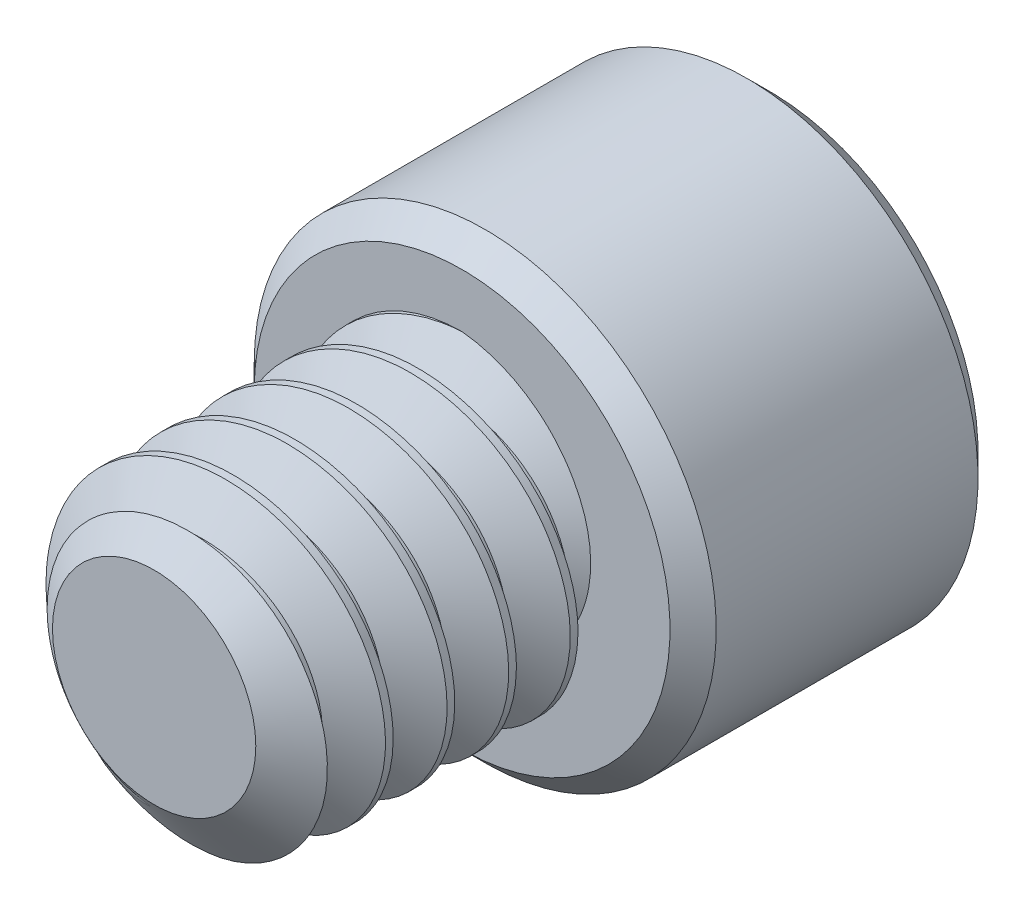
SolidWorks part; units mm, degrees
ref_plane "Front Plane" through (0, 0, 0) normal (0, 0, 1) x (1, 0, 0)
ref_plane "Top Plane" through (0, 0, 0) normal (0, 1, 0) x (1, 0, 0)
ref_plane "Right Plane" through (0, 0, 0) normal (1, 0, 0) x (0, 0, -1)
sketch "Sketch1" plane through (0, 0, 0) normal (0, 0, 1) x (1, 0, 0)
  circle A0 centre (0, 0) radius 3.175
  dimension "OD" = 6.35
extrude "Extrude1" add sketch "Sketch1" against normal blind 6.35
sketch "Sketch2" plane through (0, 0, 0) normal (0, 0, 1) x (1, 0, 0)
  circle A0 centre (0, 0) radius 3.175 construction
  circle A1 centre (0, 0) radius 3.175
curve "Helix/Spiral1" pitch 1.27 height 7.62 turns 6 parameters "pitch"=1.27
sketch "Sketch3" plane through (0, 0, 0) normal (1, 0, 0) x (0, 0, -1)
  line L0 (-1.1113, 3.175) -> (-0.635, 2.3501)
  line L1 (-0.635, 2.3501) -> (-0.4763, 2.3501)
  line L2 (-0.4763, 2.3501) -> (0, 3.175)
  line L3 (-1.1113, 3.175) -> (0, 3.175)
  line L4 (-0.5556, 3.175) -> (-0.5556, 2.3501) construction
  line L5 (-0.8731, 2.7626) -> (-0.2381, 2.7626) construction
  line L6 (0, 3.175) -> (0, -3.175) construction
  dimension "D1" = 0.1588
  dimension "D2" = 0.635
  dimension "D3" = 60
sweep "Cut-Sweep1" cut profiles "Sketch3" path "Helix/Spiral1"
sketch "Sketch4" plane through (0, 0, 0) normal (1, 0, 0) x (0, 0, -1)
  line L0 (0.7554, 3.175) -> (0, 2.0961)
  line L1 (0, 2.0961) -> (0, 3.175)
  line L2 (0.7554, 3.175) -> (0, 3.175)
  line L3 (-1.1113, 3.175) -> (0, 3.175) construction
  line L4 (0, 0) -> (7.0209, 0) construction
  dimension "D1" = 55
  dimension "D2" = 0.254
revolve "Cut-Revolve1" cut sketch "Sketch4" angle 360 about L4
sketch "Sketch5" plane through (0, 0, 0) normal (1, 0, 0) x (0, 0, -1)
  line L0 (6.35, -2.3728) -> (6.35, 2.2654) construction
  line L1 (6.35, 3.302) -> (87.4327, 3.302)
  line L2 (6.35, 3.302) -> (6.35, 0)
  line L3 (6.35, 0) -> (87.3125, 0)
  line L4 (87.3125, 2.9718) -> (87.3125, 0)
  line L5 (87.4327, 3.302) -> (87.3125, 2.9718)
  line L6 (0, 0) -> (9.9695, 0) construction
  point P3 (87.3125, 3.302)
  point P10 (87.3125, 3.302)
  dimension "D1" = 0.3302
  dimension "Thread min" = 87.3125
  dimension "D2" = 0.127
  dimension "D3" = 20
revolve "partially thread" [suppressed] add sketch "Sketch5" angle 360 about L6
sketch "Sketch6" plane through (0, 0, -6.35) normal (0, 0, -1) x (-1, 0, 0)
  circle A0 centre (0, 0) radius 4.7625
  dimension "head dia" = 9.525
extrude "Extrude2" add sketch "Sketch6" along normal blind 6.35
sketch "Sketch7" plane through (0, 0, -12.7) normal (0, 0, -1) x (-1, 0, 0)
  line L1 (0, 2.7496) -> (-2.3812, 1.3748)
  line L2 (-2.3812, 1.3748) -> (-2.3812, -1.3748)
  line L3 (-2.3812, -1.3748) -> (0, -2.7496)
  line L4 (0, -2.7496) -> (2.3813, -1.3748)
  line L5 (2.3813, -1.3748) -> (2.3813, 1.3748)
  line L6 (2.3813, 1.3748) -> (0, 2.7496)
  circle A0 centre (0, 0) radius 2.3813 construction
  dimension "hex dia" = 4.7625
extrude "Cut-Extrude1" cut sketch "Sketch7" against normal blind 3.5719
sketch "Sketch8" plane through (0, 0, -12.7) normal (0, 0, -1) x (-1, 0, 0)
  circle A0 centre (0, 0) radius 2.7496
extrude "Cut-Extrude2" cut sketch "Sketch8" against normal through all draft 45
chamfer "Chamfer1" distance 0.4763 angle 45 2 edges at (-4.7625, 0, -12.7) (-4.7625, 0, -6.35)
sketch "Sketch9" plane through (0, 0, 0) normal (1, 0, 0) x (0, 0, -1)
  line L0 (0, 3.175) -> (0, -3.175) construction
  line L1 (6.985, 3.175) -> (6.985, -3.175) construction
  dimension "D1" = 6.985
equation "\"D3@Helix/Spiral1\" = \"screw length@Extrude1\"+\"pitch@Helix/Spiral1\""
equation "\"D1@Sketch3\" = \"pitch@Helix/Spiral1\"*.125"
equation "\"D2@Sketch3\" = \"pitch@Helix/Spiral1\"*.5"
equation "\"D1@Cut-Extrude1\" = \"hex dia@Sketch7\"*.75"
equation "\"D1@Chamfer1\" = \"head dia@Sketch6\"*.05"
equation "\"D1@Sketch9\" = \"pitch@Helix/Spiral1\"*5.5"
